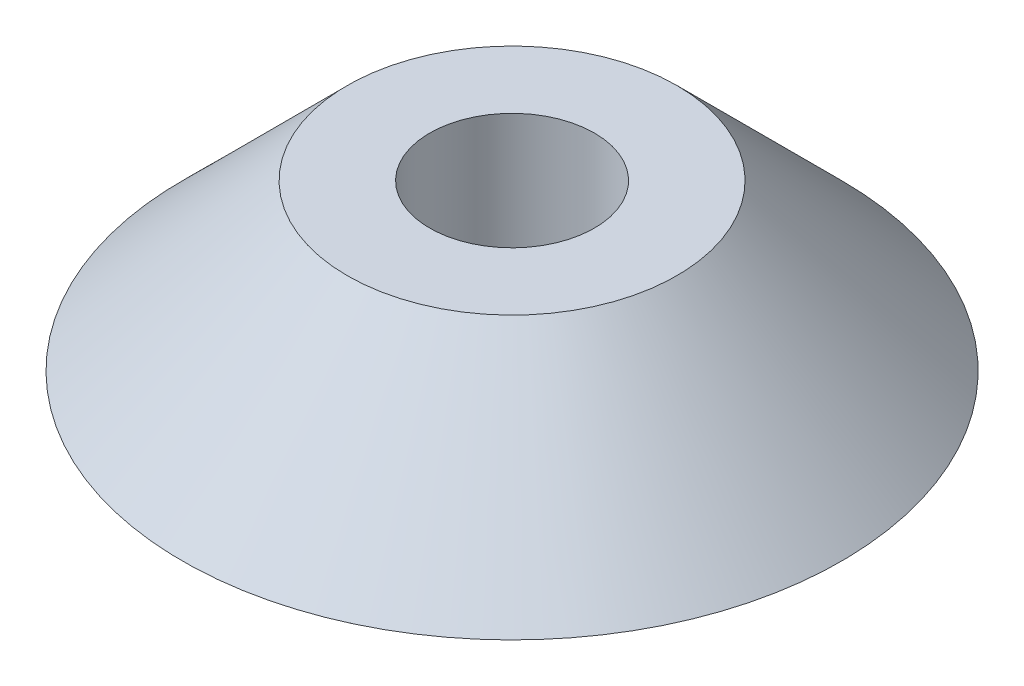
SolidWorks part; units mm, degrees
ref_plane "Front Plane" through (0, 0, 0) normal (0, 0, 1) x (1, 0, 0)
ref_plane "Top Plane" through (0, 0, 0) normal (0, 1, 0) x (1, 0, 0)
ref_plane "Right Plane" through (0, 0, 0) normal (1, 0, 0) x (0, 0, -1)
sketch "Sketch1" plane through (0, 0, 0) normal (0, 0, 1) x (1, 0, 0)
  line L0 (0, -1000.6938) -> (0, 48999.3062) construction
  line L1 (6.35, 0) -> (25.4, 0)
  line L2 (25.4, 0) -> (12.7, 12.7)
  line L3 (12.7, 12.7) -> (6.35, 12.7)
  line L4 (6.35, 12.7) -> (0, 12.7) construction
  line L5 (6.35, 12.7) -> (6.35, 0)
  line L6 (0, 0) -> (6.35, 0) construction
  dimension "D1" = 45
  dimension "D2" = 12.7
  dimension "D3" = 25.4
  dimension "D4" = 12.7
revolve "Revolve1" add sketch "Sketch1" angle 360 about L0
ref_axis "Axis1" through (0, 12.7, 0) along (0, -1, 0)
ref_plane "Plane1" through (0, 22.225, 0) normal (0, 1, 0) x (1, 0, 0)
ref_axis "Axis2" through (27.94, 22.225, 0) along (-1, 0, 0)
